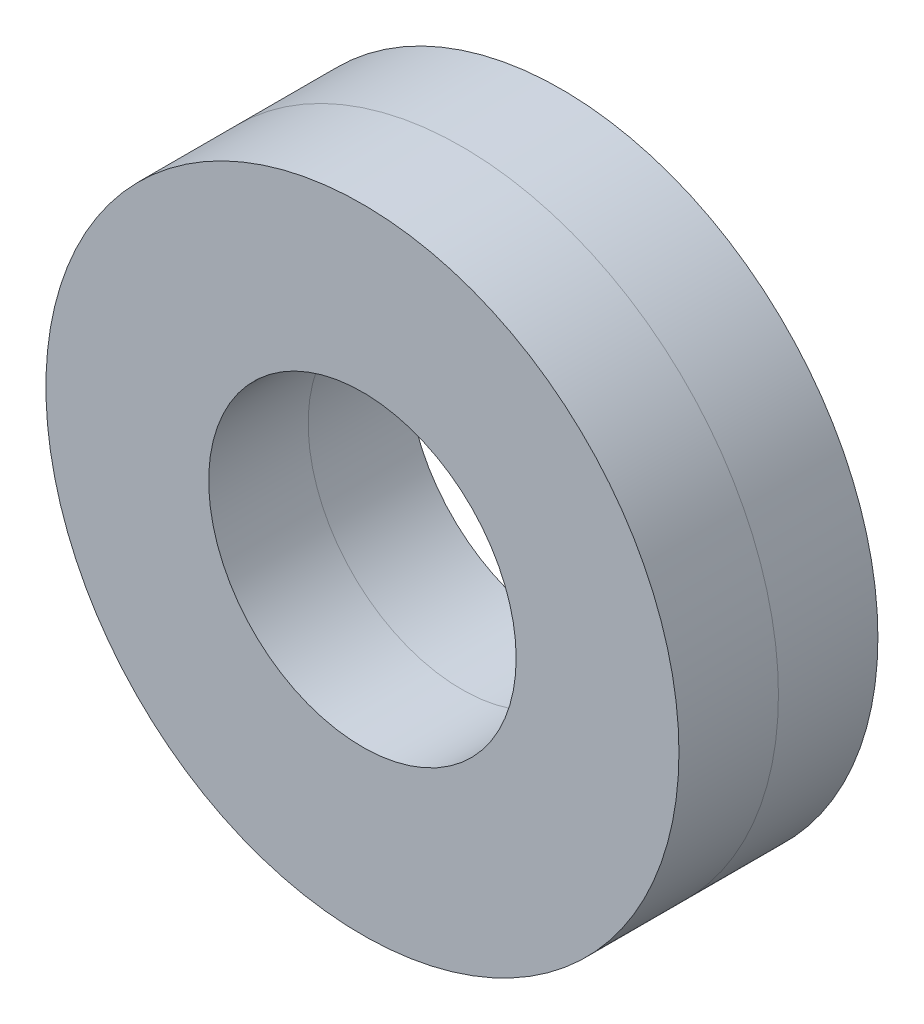
SolidWorks part; units mm, degrees
ref_plane "前视基准面" through (0, 0, 0) normal (0, 0, 1) x (1, 0, 0)
ref_plane "上视基准面" through (0, 0, 0) normal (0, 1, 0) x (1, 0, 0)
ref_plane "右视基准面" through (0, 0, 0) normal (1, 0, 0) x (0, 0, -1)
sketch "草图8" plane through (0, 0, 0) normal (1, 0, 0) x (0, 0, -1)
  line L0 (0, -3.5) -> (0, 3.5)
  line L1 (-1.1, 3.5) -> (1.1, 3.5)
  line L2 (1.1, 3.5) -> (1.1, 1.7)
  line L3 (1.1, 1.7) -> (-1.1, 1.7)
  line L4 (0, 0) -> (1.1754, 0)
  line L5 (-1.1, 3.5) -> (-1.1, 1.7)
  line L6 (-1.1, -3.5) -> (1.1, -3.5)
  line L7 (1.1, -1.7) -> (-1.1, -1.7)
  line L8 (-1.1, 1.7) -> (-1.1, -3.5)
  line L9 (1.1, 1.7) -> (1.1, -3.5)
  point P9 (0, 1.7)
  dimension "D1" = 3.4
  dimension "D2" = 7
  dimension "D3" = 2.2
revolve "旋转3" add sketch "草图8" angle 360 about L4 region at (0, 2.6, 0.55)
revolve "旋转4" add sketch "草图8<8>" angle 360 about L4 region at (0, 2.6, -0.55)
sketch "草图8<8>" plane through (0, 0, 0) normal (1, 0, 0) x (0, 0, -1) same geometry as "草图8"
